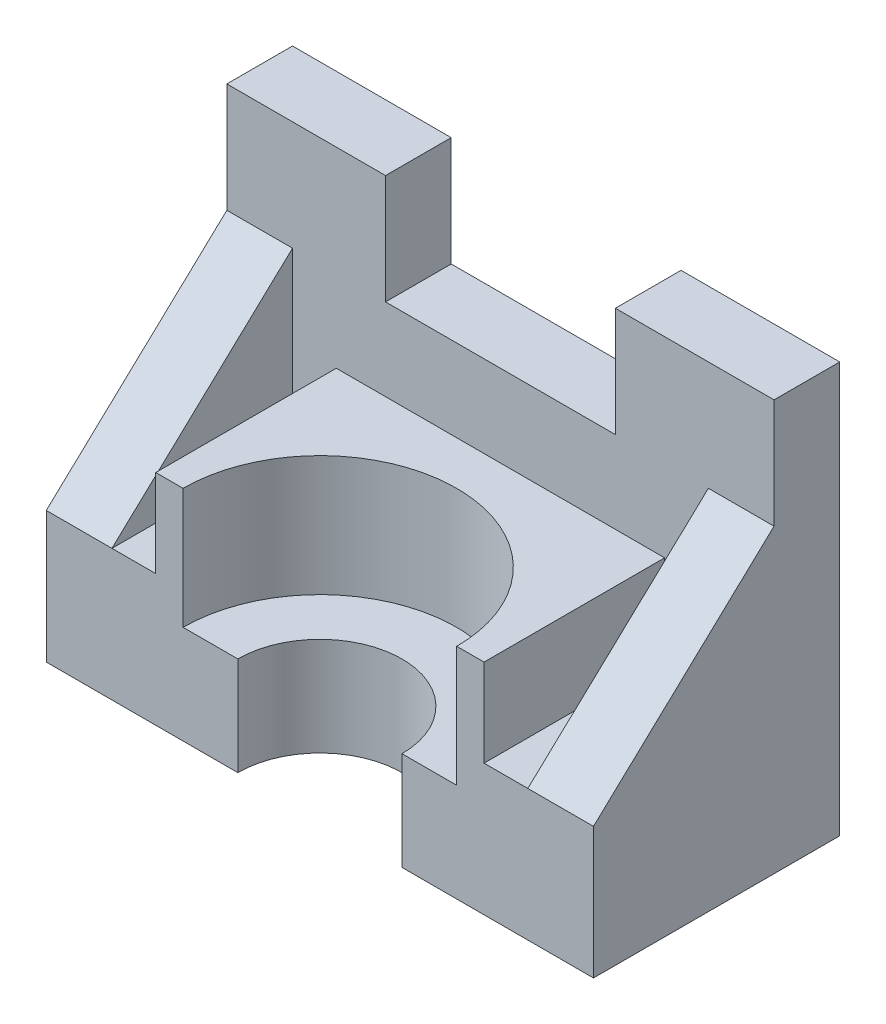
SolidWorks part; units mm, degrees
ref_plane "Front Plane" through (0, 0, 0) normal (0, 0, 1) x (1, 0, 0)
ref_plane "Top Plane" through (0, 0, 0) normal (0, 1, 0) x (1, 0, 0)
ref_plane "Right Plane" through (0, 0, 0) normal (1, 0, 0) x (0, 0, -1)
sketch "Sketch1" plane through (0, 0, 0) normal (0, 1, 0) x (1, 0, 0)
  line L0 (-60.83, -17.4203) -> (-48.83, -17.4203)
  line L1 (-60.83, 27.5797) -> (39.17, 27.5797)
  line L2 (-60.83, 27.5797) -> (-60.83, -17.4203)
  line L3 (-60.83, -17.4203) -> (-25.83, -17.4203)
  line L4 (39.17, 27.5797) -> (39.17, -17.4203)
  line L5 (-48.83, -17.4203) -> (-48.83, 15.5797)
  line L6 (39.17, 15.5797) -> (-60.83, 15.5797)
  line L7 (39.17, -17.4203) -> (27.17, -17.4203)
  line L8 (27.17, -17.4203) -> (27.17, 15.5797)
  line L9 (-48.83, 15.5797) -> (-31.83, 15.5797)
  line L10 (-31.83, 15.5797) -> (-31.83, 27.5797)
  line L11 (-31.83, 27.5797) -> (10.17, 27.5797)
  line L12 (10.17, 27.5797) -> (10.17, 15.5797)
  line L13 (-35.83, -17.4203) -> (-40.83, -17.4203)
  line L14 (-40.83, -17.4203) -> (-40.83, 15.5797)
  line L15 (14.17, -17.4203) -> (19.17, -17.4203)
  line L16 (19.17, -17.4203) -> (19.17, 15.5797)
  line L17 (4.17, -17.4203) -> (39.17, -17.4203)
  arc A0 (14.17, -17.4203) -> (-35.83, -17.4203) centre (-10.83, -17.4203) ccw
  arc A1 (4.17, -17.4203) -> (-25.83, -17.4203) centre (-10.83, -17.4203) ccw
extrude "Boss-Extrude3" add sketch "Sketch1" along normal blind 18 contours A1 L17 A0 L3 region at (-10.83, 0, -7.0207)
extrude "Boss-Extrude4" add sketch "Sketch1<7>" along normal blind 24 separate body contours L3 L14 L9 L5 | L16 L17 L8 L6 region at (-44.83, 0, 0.9203) region at (23.17, 0, 0.9203)
sketch "Sketch1<7>" plane through (0, 0, 0) normal (0, 1, 0) x (1, 0, 0) same geometry as "Sketch1"
extrude "Boss-Extrude5" add sketch "Sketch1<8>" along normal blind 55 contours L5 L6 L2 L0 | L8 L7 L4 L6 region at (-54.83, 0, 0.9203) region at (33.17, 0, 0.9203)
sketch "Sketch1<8>" plane through (0, 0, 0) normal (0, 1, 0) x (1, 0, 0) same geometry as "Sketch1"
sketch "Sketch2" plane through (-60.83, 0, 0) normal (-1, 0, 0) x (0, 0, 1)
  line L0 (17.4203, 55) -> (17.4203, 24)
  line L1 (17.4203, 55) -> (17.4203, 0) construction
  line L2 (17.4203, 24) -> (-15.5797, 55)
  line L3 (-15.5797, 55) -> (17.4203, 55)
extrude "Cut-Extrude1" cut sketch "Sketch2" against normal blind 1000
extrude "Boss-Extrude6" add sketch "Sketch1<9>" along normal blind 75 contours L6 L10 L1 L2 L9 | L1 L12 L6 L4 region at (-46.33, 0, -21.5797) region at (24.67, 0, -21.5797)
sketch "Sketch1<9>" plane through (0, 0, 0) normal (0, 1, 0) x (1, 0, 0) same geometry as "Sketch1"
extrude "Boss-Extrude7" add sketch "Sketch1<10>" along normal blind 55 contours L12 L1 L10 L6 region at (-10.83, 0, -21.5797)
sketch "Sketch1<10>" plane through (0, 0, 0) normal (0, 1, 0) x (1, 0, 0) same geometry as "Sketch1"
extrude "Boss-Extrude8" add sketch "Sketch1<11>" along normal blind 40 contours A0 L15 L16 L6 L14 L3 region at (-40.1452, 0, 0.9203)
sketch "Sketch1<11>" plane through (0, 0, 0) normal (0, 1, 0) x (1, 0, 0) same geometry as "Sketch1"
